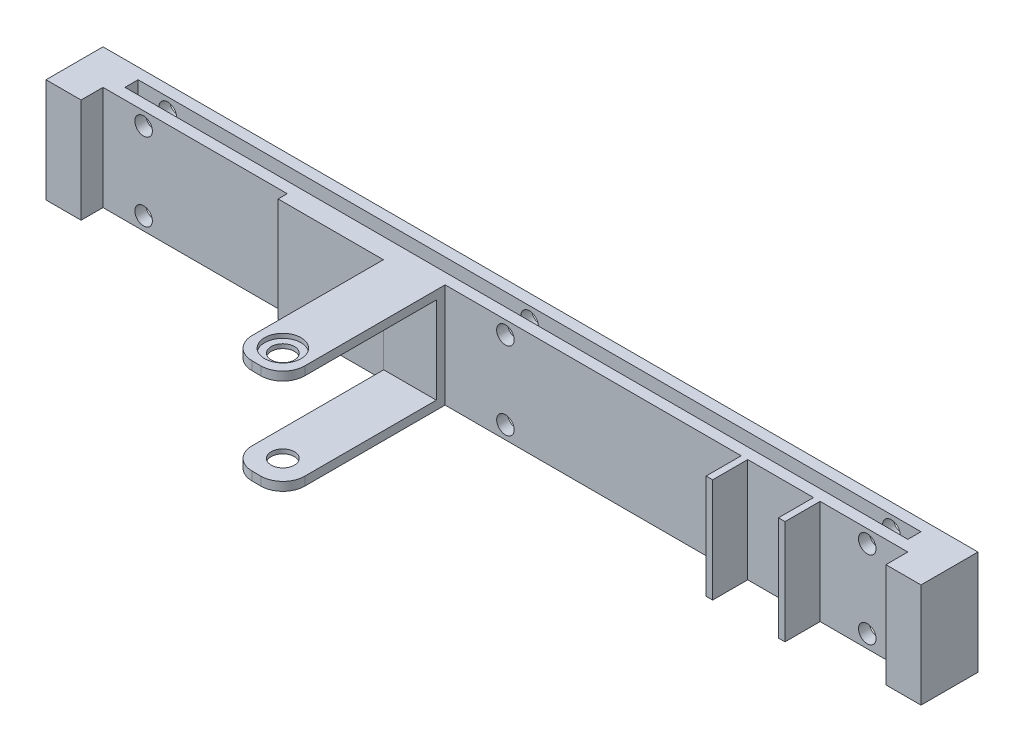
SolidWorks part; units mm, degrees
ref_plane "Front Plane" through (0, 0, 0) normal (1, 0, 0) x (0, 1, 0)
ref_plane "Top Plane" through (0, 0, 0) normal (0, 0, 1) x (0, 1, 0)
ref_plane "Right Plane" through (0, 0, 0) normal (0, 1, 0) x (-1, 0, 0)
sketch "Sketch2" plane through (0, 0, 0) normal (0, 0, 1) x (0, 1, 0)
  line L1 (-71.25, 0) -> (-95, 0)
  line L2 (-71.25, 0) -> (-71.25, 12)
  line L3 (-71.25, 12) -> (-95, 12)
  line L4 (-95, 0) -> (-95, 12)
extrude "Boss-Extrude1" add sketch "Sketch2" along normal blind 10
sketch "Sketch3" plane through (0, 0, 10) normal (0, 0, 1) x (1, 0, 0)
  line L1 (-12, -71.25) -> (0, -71.25)
  line L2 (-12, -71.25) -> (-12, -73.225)
  line L3 (-12, -73.225) -> (0, -73.225)
  line L4 (0, -71.25) -> (0, -73.225)
  line L6 (-12, -73.225) -> (0, -73.225) construction
  point P4 (-12.2988, -57.5889)
  point P5 (-12.2881, -57.8606)
  point P6 (-0.2881, -69.4546)
  point P7 (0, 0)
  point P8 (-12, -71.25)
  point P9 (0, -71.25)
  dimension "D1" = 1.975
extrude "Boss-Extrude2" add sketch "Sketch3" along normal blind 35
fillet "Fillet1" radius 5 2 edges at (0, -72.2375, 45) (-12, -72.2375, 45)
ref_plane "Plane1" through (0, -83.125, 0) normal (0, 1, 0) x (1, 0, 0)
mirror "Mirror1" about plane through (0, -83.125, 0) normal (0, 1, 0) of "Fillet1", "Boss-Extrude2"
sketch "Sketch5" plane through (0, -95, 0) normal (0, -1, 0) x (1, 0, 0)
  line L1 (-6, 45) -> (-12, 45)
  line L2 (-6, 45) -> (-6, 39)
  line L3 (-6, 39) -> (-12, 39)
  line L4 (-12, 45) -> (-12, 39)
  line L5 (-5, 45) -> (-7, 45) construction
  line L6 (-12, 40) -> (-12, 0) construction
  circle A0 centre (-6, 39) radius 2.65
  point P4 (-11.1692, 42.7601)
  point P5 (-12, 45)
  point P6 (-12, 39)
  point P9 (0, 44.6613)
  point P10 (-6, 45)
  point P13 (-7, 45)
  dimension "D1" = 6
extrude "Cut-Extrude1" cut sketch "Sketch5" against normal through all contours A0
sketch "Sketch6" plane through (0, -95, 0) normal (0, -1, 0) x (1, 0, 0)
  line L1 (-6, 45) -> (-12, 45)
  line L2 (-6, 45) -> (-6, 39)
  line L3 (-6, 39) -> (-12, 39)
  line L4 (-12, 45) -> (-12, 39)
  line L6 (-5, 45) -> (-7, 45) construction
  line L7 (-12, 40) -> (-12, 0) construction
  circle A0 centre (-6, 39) radius 4.15
  point P4 (-6, 45)
  point P7 (-12, 39)
  dimension "D1" = 6
extrude "Cut-Extrude2" cut sketch "Sketch6" against normal blind 1 contours A0
mirror "Mirror2" about plane through (0, -83.125, 0) normal (0, 1, 0) of "Cut-Extrude2"
sketch "Sketch7" plane through (0, 0, 0) normal (0, 0, -1) x (1, 0, 0)
  line L1 (-6, 95) -> (-86, 95)
  line L2 (-6, 95) -> (-6, 71.25)
  line L3 (-6, 71.25) -> (-86, 71.25)
  line L4 (-86, 95) -> (-86, 71.25)
  line L5 (-6, 95) -> (113.5, 95)
  line L6 (-6, 95) -> (-6, 71.25)
  line L7 (-6, 71.25) -> (113.5, 71.25)
  line L8 (113.5, 95) -> (113.5, 71.25)
  line L10 (-12, 95) -> (0, 95) construction
  line L11 (0, 71.25) -> (-12, 71.25) construction
  point P4 (-21.4335, 40.5369)
  point P7 (-21.4335, 40.5369)
  point P8 (-27.4335, 135.7869)
  point P9 (-27.4335, 107.2408)
  point P10 (-27.4335, 66.4523)
  point P11 (-27.4335, 40.5369)
  point P12 (-6, 95)
  point P15 (-6, 71.25)
  line M20 (0, 71.25) -> (0, 95)
  line M22 (-12, 95) -> (-12, 71.25)
  dimension "D1" = 80
  dimension "D2" = 119.5
extrude "Boss-Extrude3" add sketch "Sketch7" against normal blind 8 contours L1 L4 L3 M22 | L8 L5 L7 M20 region at (-49, -83.125, 0) region at (56.75, -83.125, 0)
sketch "Sketch8" plane through (0, 0, 8) normal (0, 0, 1) x (1, 0, 0)
  line L1 (113.5, -71.25) -> (105.5, -71.25)
  line L2 (113.5, -71.25) -> (113.5, -95)
  line L3 (113.5, -95) -> (105.5, -95)
  line L4 (105.5, -71.25) -> (105.5, -95)
  line L6 (-86, -71.25) -> (-78, -71.25)
  line L7 (-86, -71.25) -> (-86, -95)
  line L8 (-86, -95) -> (-78, -95)
  line L9 (-78, -71.25) -> (-78, -95)
  point P4 (-86, -95)
  point P5 (-86, -71.25)
  point P6 (0, 0)
  point P11 (113.5, -71.25)
  point P12 (113.5, -95)
  dimension "D2" = 8
extrude "Boss-Extrude4" add sketch "Sketch8" along normal blind 5
sketch "Sketch10" plane through (-12, 0, 0) normal (-1, 0, 0) x (0, -1, 0)
  line L0 (95, 40) -> (95, 8) construction
  line L1 (71.25, 8) -> (95, 8)
  line L2 (71.25, 8) -> (71.25, 10.0757)
  line L3 (71.25, 10.0757) -> (95, 10.0757)
  line L4 (95, 8) -> (95, 10.0757)
extrude "Boss-Extrude5" add sketch "Sketch10" along normal blind 24
sketch "Sketch11" plane through (0, -71.25, 0) normal (0, 1, 0) x (-1, 0, 0)
  line L1 (78, 0) -> (-105.5, 0)
  line L2 (78, 0) -> (78, 8)
  line L3 (78, 8) -> (-105.5, 8)
  line L4 (-105.5, 0) -> (-105.5, 8)
  line L5 (75.5, 5.5) -> (-103, 5.5)
  line L6 (-103, 2.5) -> (-103, 5.5)
  line L7 (75.5, 2.5) -> (-103, 2.5)
  line L8 (75.5, 2.5) -> (75.5, 5.5)
  line L11 (-113.5, 0) -> (86, 0) construction
  line L12 (86, 0) -> (78, 0)
  line L13 (86, 0) -> (86, 10.0757)
  line L14 (86, 10.0757) -> (78, 10.0757)
  line L15 (78, 0) -> (78, 10.0757)
  point P0 (-105.5, 8)
  point P5 (76, 0.5043)
  dimension "D1" = 2.5
extrude "Cut-Extrude3" cut sketch "Sketch11" against normal blind 6 contours L7 L8 L5 L6 region at (13.75, -71.25, 4)
mirror "Mirror3" about plane through (0, -83.125, 0) normal (0, 1, 0) of "Cut-Extrude3"
sketch "Sketch12" plane through (0, 0, 10.0757) normal (0, 0, 1) x (1, 0, 0)
  line L1 (-78, -71.25) -> (-68.75, -71.25)
  line L2 (-78, -71.25) -> (-78, -74.25)
  line L3 (-78, -74.25) -> (-68.75, -74.25)
  line L4 (-68.75, -71.25) -> (-68.75, -74.25)
  circle A0 centre (-68.75, -74.25) radius 2
  dimension "D3" = 4
  dimension "D1" = 9.25
  dimension "D2" = 3
extrude "Cut-Extrude4" cut sketch "Sketch12" against normal through all and the other way through all contours A0
pattern_linear "LPattern1" count 3 spacing 82.5 along (1, 0, 0) count 2 spacing 17.75 along (0, -1, 0) of "Cut-Extrude4"
sketch "Sketch14" plane through (0, 0, 8) normal (0, 0, 1) x (1, 0, 0)
  line L0 (0, -95) -> (105.5, -95) construction
  line L1 (105.5, -71.25) -> (85.5, -71.25)
  line L2 (105.5, -71.25) -> (105.5, -95)
  line L3 (105.5, -95) -> (85.5, -95)
  line L4 (85.5, -71.25) -> (85.5, -95)
  line L6 (85.5, -71.25) -> (84, -71.25)
  line L7 (85.5, -71.25) -> (85.5, -95)
  line L8 (85.5, -95) -> (84, -95)
  line L9 (84, -71.25) -> (84, -95)
  line L10 (84, -71.25) -> (69, -71.25)
  line L11 (84, -71.25) -> (84, -95)
  line L12 (84, -95) -> (69, -95)
  line L13 (69, -71.25) -> (69, -95)
  line L14 (69, -71.25) -> (67.5, -71.25)
  line L15 (69, -71.25) -> (69, -95)
  line L16 (69, -95) -> (67.5, -95)
  line L17 (67.5, -71.25) -> (67.5, -95)
  line M22 (105.5, -71.25) -> (0, -71.25)
  line M24 (0, -95) -> (105.5, -95)
  dimension "D1" = 20
  dimension "D2" = 1.5
  dimension "D3" = 15
  dimension "D4" = 1.5
extrude "Boss-Extrude6" add sketch "Sketch14" along normal blind 8 contours L17 L13 M22 M24 | L9 L4 M22 M24 region at (84.75, -83.125, 8) region at (68.25, -83.125, 8)
equation "\"whitekey_cutout_length\"= 101.5"
equation "\"mount_recess_length\"=50"
equation "\"mount_recess_height\"=12.5"
equation "\"mount_recess_depth\"=1.5"
equation "\"wall_thickness\"=8"
equation "\"base_mount_height\"=35"
equation "\"D1@Boss-Extrude2\"=\"base_mount_height\""
equation "\"D1@Sketch7\"=\"base_rear_length\""
equation "\"D2@Sketch7\"=\"wall_thickness\"+110+1.5"
equation "\"base_rear_length\"=80"
equation "\"D1@Boss-Extrude3\"=\"wall_thickness\""
equation "\"D1@Sketch8\"=\"wall_thickness\""
equation "\"D2@Sketch8\"=\"wall_thickness\""
